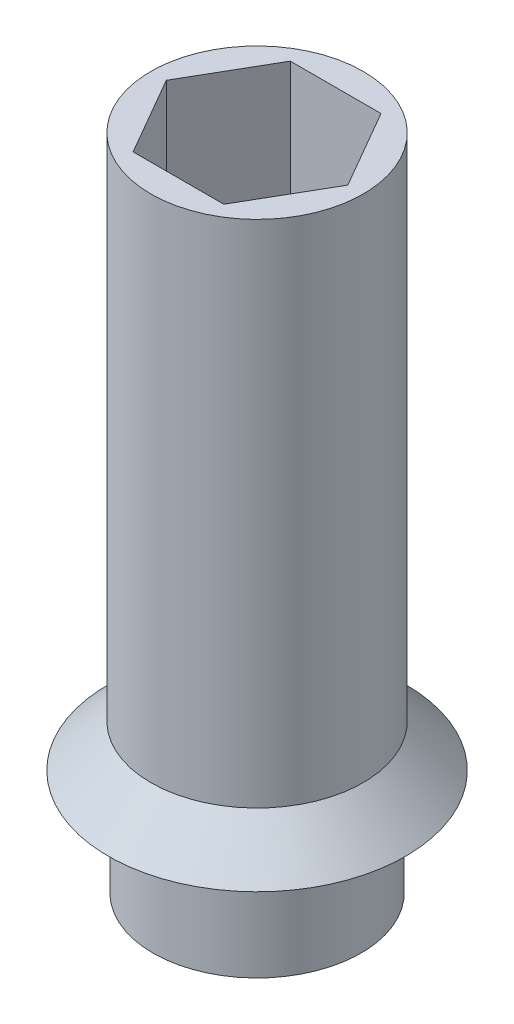
SolidWorks part; units mm, degrees
ref_plane "前视基准面" through (0, 0, 0) normal (0, 0, 1) x (1, 0, 0)
ref_plane "上视基准面" through (0, 0, 0) normal (0, 1, 0) x (1, 0, 0)
ref_plane "右视基准面" through (0, 0, 0) normal (1, 0, 0) x (0, 0, -1)
sketch "草图1" plane through (0, 0, 0) normal (0, 1, 0) x (1, 0, 0)
  line L1 (4.2724, 0) -> (2.1362, 3.7)
  line L2 (2.1362, 3.7) -> (-2.1362, 3.7)
  line L3 (-2.1362, 3.7) -> (-4.2724, 0)
  line L4 (-4.2724, 0) -> (-2.1362, -3.7)
  line L5 (-2.1362, -3.7) -> (2.1362, -3.7)
  line L6 (2.1362, -3.7) -> (4.2724, 0)
  circle A0 centre (0, 0) radius 3.7 construction
  circle A1 centre (0, 0) radius 4.9
  dimension "D2" = 9.8
  dimension "D1" = 7.4
extrude "凸台-拉伸1" add sketch "草图1" along normal blind 5
sketch "草图2" plane through (0, 5, 0) normal (0, 1, 0) x (1, 0, 0)
  line L1 (4.2724, 0) -> (2.1362, 3.7)
  line L2 (2.1362, 3.7) -> (-2.1362, 3.7)
  line L3 (-2.1362, 3.7) -> (-4.2724, 0)
  line L4 (-4.2724, 0) -> (-2.1362, -3.7)
  line L5 (-2.1362, -3.7) -> (2.1362, -3.7)
  line L6 (2.1362, -3.7) -> (4.2724, 0)
  circle A1 centre (0, 0) radius 3.7 construction
  circle A2 centre (0, 0) radius 5
  dimension "D1" = 10
extrude "凸台-拉伸2" add sketch "草图2" along normal blind 26
sketch "草图5" plane through (0, 5, 0) normal (0, -1, 0) x (1, 0, 0)
  circle A0 centre (0, 0) radius 7
  circle A1 centre (0, 0) radius 5
  circle A2 centre (0, 0) radius 5 construction
  dimension "D1" = 14
extrude "凸台-拉伸4" add sketch "草图5" against normal blind 2
chamfer "倒角1" distance 2 angle 45 1 edges at (0, 7, -7)
